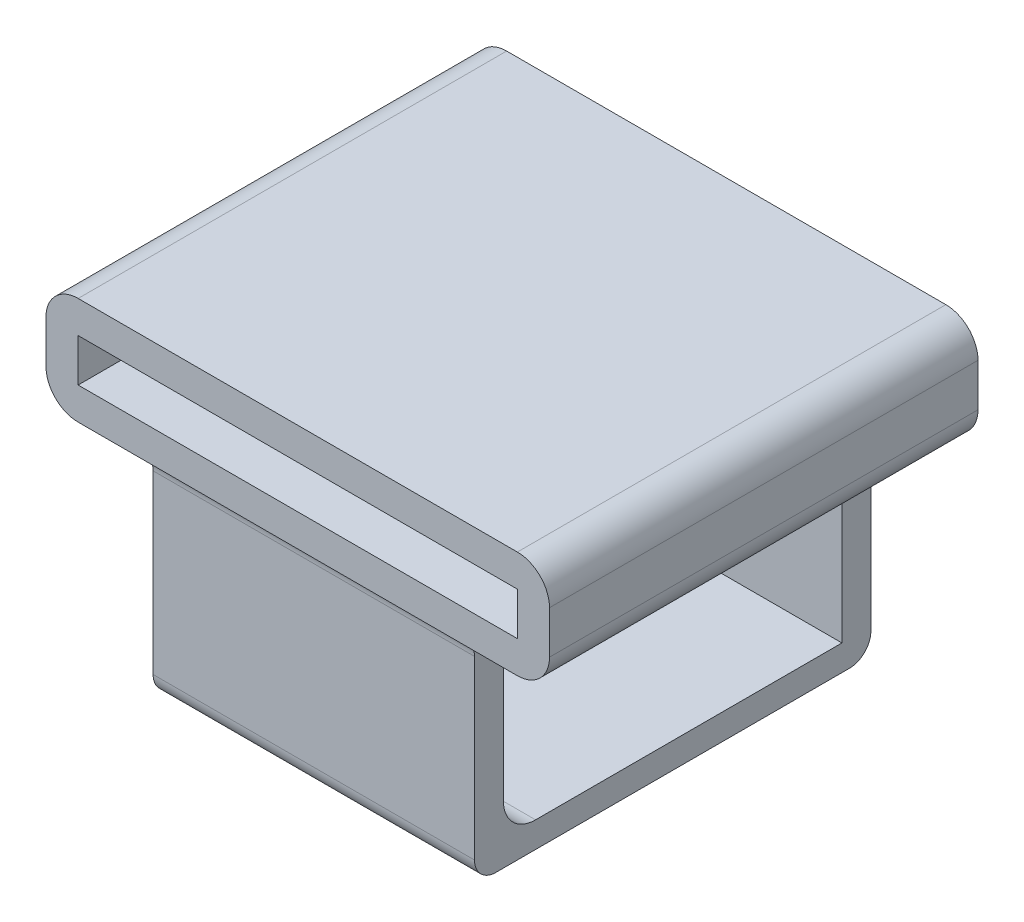
SolidWorks part; units mm, degrees
ref_plane "Alzado" through (0, 0, 0) normal (0, 0, 1) x (1, 0, 0)
ref_plane "Planta" through (0, 0, 0) normal (0, 1, 0) x (1, 0, 0)
ref_plane "Vista lateral" through (0, 0, 0) normal (1, 0, 0) x (0, 0, -1)
sketch "Croquis1" plane through (0, 0, 0) normal (0, 0, 1) x (1, 0, 0)
  line L0 (1.5, -1.5) -> (1.5, 3.5)
  line L1 (0, 0) -> (-20.5, 0)
  line L2 (0, 0) -> (0, 2)
  line L3 (0, 2) -> (-20.5, 2)
  line L4 (-20.5, 0) -> (-20.5, 2)
  line L5 (1.5, 3.5) -> (-22, 3.5)
  line L6 (-22, -1.5) -> (-22, 3.5)
  line L7 (1.5, -1.5) -> (-22, -1.5)
  dimension "D1" = 20.5
  dimension "D2" = 2
  dimension "D3" = 1.5
extrude "Saliente-Extruir1" add sketch "Croquis1" along normal blind 20
sketch "Croquis5" plane through (0, -1.5, 0) normal (0, -1, 0) x (1, 0, 0)
  line L0 (-22, 20) -> (-22, 0) construction
  line L1 (-17.75, 19.25) -> (-2.75, 19.25)
  line L2 (-17.75, 19.25) -> (-17.75, 0.75)
  line L3 (-17.75, 0.75) -> (-2.75, 0.75)
  line L4 (-2.75, 19.25) -> (-2.75, 0.75)
  line L5 (-22, 20) -> (1.5, 20) construction
  point P4 (-17.75, 10)
  point P7 (-22, 10)
  point P10 (-10.25, 19.25)
  point P11 (-10.25, 20)
  dimension "D1" = 15
  dimension "D2" = 18.5
extrude "Saliente-Extruir3" add sketch "Croquis5" along normal blind 10.2
sketch "Croquis6" plane through (-17.75, 0, 0) normal (-1, 0, 0) x (0, 0, 1)
  line L0 (19.25, -11.7) -> (0.75, -11.7) construction
  line L1 (17.9, -10.5) -> (2.1, -10.5)
  line L2 (17.9, -10.5) -> (17.9, -2.3)
  line L3 (17.9, -2.3) -> (2.1, -2.3)
  line L4 (2.1, -10.5) -> (2.1, -2.3)
  point P4 (10, -10.5)
  point P7 (10, -11.7)
  dimension "D1" = 8.2
  dimension "D2" = 1.2
  dimension "D3" = 15.8
extrude "Cortar-Extruir2" cut sketch "Croquis6" against normal up to vertex (15 mm away) up to point (-2.75, -11.7, 0.75)
fillet "Redondeo3" radius 1.5 2 edges at (-10.25, -10.5, 17.9) (-10.25, -2.3, 17.9)
sketch "Croquis7" plane through (-17.75, 0, 0) normal (-1, 0, 0) x (0, 0, 1)
  line L17 (2.1, -10.5) -> (16.4, -10.5) construction
  line L18 (17.9, -11) -> (2.1, -11)
  line L19 (18.4, -10.5) -> (18.4, -2.3)
  line L20 (17.9, -1.8) -> (2.1, -1.8)
  line L21 (1.6, -10.5) -> (1.6, -2.3)
  line L22 (2.1, -2.3) -> (2.1, -10.5) construction
  line L23 (17.9, -9) -> (17.9, -3.8) construction
  line L24 (16.4, -2.3) -> (2.1, -2.3) construction
  arc A4 (2.1, -11) -> (1.6, -10.5) centre (2.1, -10.5) cw
  arc A5 (2.1, -1.8) -> (1.6, -2.3) centre (2.1, -2.3) ccw
  arc A6 (18.4, -2.3) -> (17.9, -1.8) centre (17.9, -2.3) ccw
  arc A7 (17.9, -11) -> (18.4, -10.5) centre (17.9, -10.5) ccw
  point P8 (9.25, -2.3)
  dimension "D5" = 0.5
  dimension "D1" = 0.5
  dimension "D2" = 0.5
  dimension "D3" = 0.5
  dimension "D4" = 0.5
extrude "Cortar-Extruir3" cut sketch "Croquis7" against normal blind 3
fillet "Redondeo4" radius 1 4 edges at (-10.25, -1.5, 0.75) (-10.25, -11.7, 0.75) (-10.25, -11.7, 19.25) (-10.25, -1.5, 19.25)
fillet "Redondeo5" radius 1.5 4 edges at (1.5, 3.5, 10) (1.5, -1.5, 10) (-22, 3.5, 10) (-22, -1.5, 10)
